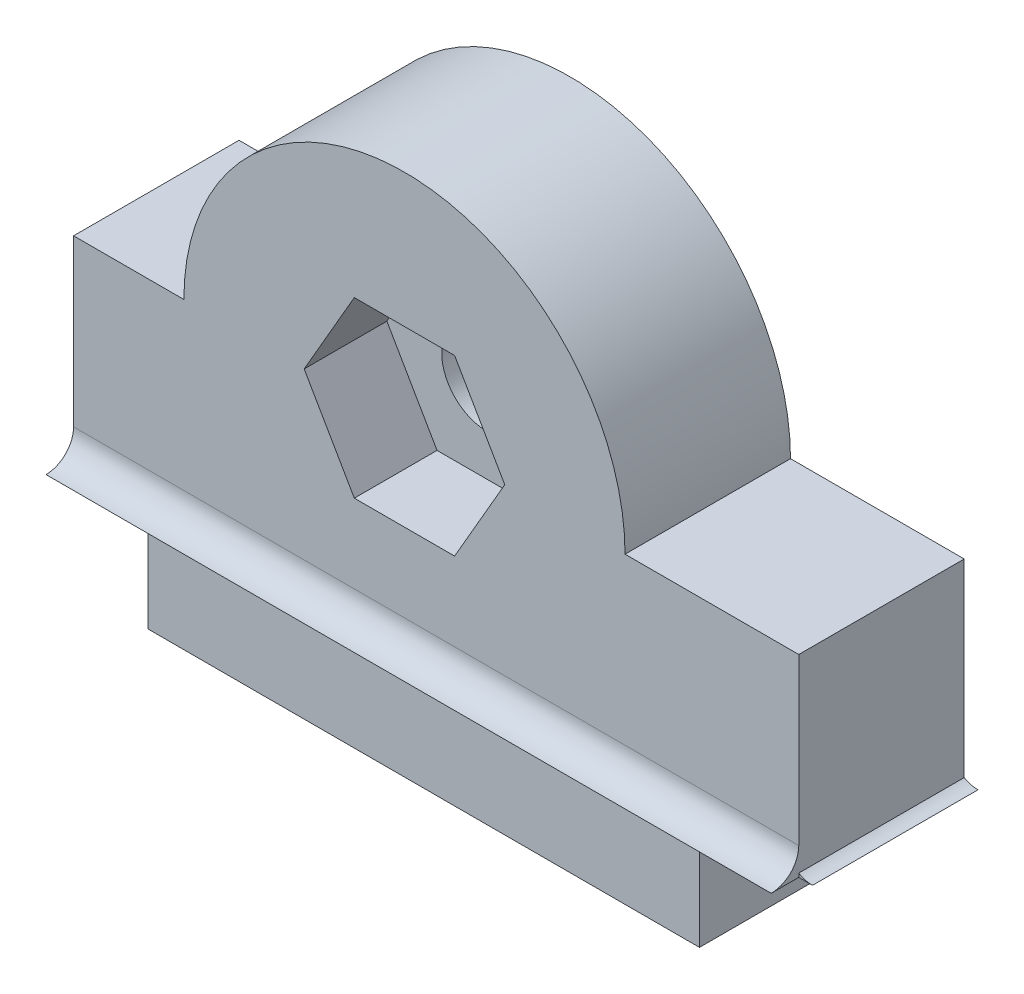
SolidWorks part; units mm, degrees
ref_plane "Front Plane" through (0, 0, 0) normal (0, 0, 1) x (1, 0, 0)
ref_plane "Top Plane" through (0, 0, 0) normal (0, 1, 0) x (1, 0, 0)
ref_plane "Right Plane" through (0, 0, 0) normal (1, 0, 0) x (0, 0, -1)
sketch "Sketch1" plane through (0, 0, 0) normal (0, 0, 1) x (1, 0, 0)
  line L0 (0, 0) -> (20, 0)
  line L1 (0, 0) -> (0, 4)
  line L2 (20, 0) -> (20, 4)
  line L3 (0, 4) -> (-2.7, 4)
  line L4 (23.6, 11) -> (23.6, 4)
  line L5 (-2.7, 4) -> (-2.7, 11)
  line L6 (-2.7, 11) -> (1.3, 11)
  line L7 (17.3, 11) -> (23.6, 11)
  line L8 (23.6, 4) -> (20, 4)
  line L11 (11.1187, 14.15) -> (7.4813, 14.15)
  line L12 (7.4813, 14.15) -> (5.6627, 11)
  line L13 (5.6627, 11) -> (7.4813, 7.85)
  line L14 (7.4813, 7.85) -> (11.1187, 7.85)
  line L15 (11.1187, 7.85) -> (12.9373, 11)
  line L16 (12.9373, 11) -> (11.1187, 14.15)
  arc A0 (17.3, 11) -> (1.3, 11) centre (9.3, 11) ccw
  circle A1 centre (9.3, 11) radius 3.15 construction
  point P19 (10, 0)
  dimension "D4" = 6.3
  dimension "D6" = 20
  dimension "D9" = 4
  dimension "D5" = 23.6
  dimension "D7" = 2.7
  dimension "D2" = 7
extrude "Boss-Extrude1" add sketch "Sketch1" along normal blind 6
sketch "Sketch2" plane through (-2.7, 0, 0) normal (-1, 0, 0) x (0, 0, 1)
  line L0 (3, 0) -> (3, 7) construction
  line L1 (6, 4) -> (6, 5)
  line L2 (6, 4) -> (7, 4)
  line L3 (0, 4) -> (-1, 4) construction
  line L4 (0, 4) -> (0, 5) construction
  arc A0 (6, 5) -> (7, 4) centre (7, 5) ccw
  arc A1 (0, 5) -> (-1, 4) centre (-1, 5) cw construction
  dimension "D1" = 1
  dimension "D2" = 1
  dimension "D3" = 6
  dimension "D4" = 3
  dimension "D5" = 4
extrude "Boss-Extrude2" add sketch "Sketch2" against normal up to surface (26.3 mm away) up to face at (23.6, 7.5, 3)
sketch "Sketch4" plane through (0, 0, 6) normal (0, 0, 1) x (1, 0, 0)
  line L0 (10.8, 0) -> (10.8, 7) construction
  line L1 (23.1, 4) -> (23.1, 5)
  line L2 (23.1, 4) -> (24.1, 4)
  line L3 (-1.5, 4) -> (-2.5, 4)
  line L4 (-1.5, 4) -> (-1.5, 5)
  arc A0 (23.1, 5) -> (24.1, 4) centre (24.1, 5) ccw
  arc A1 (-1.5, 5) -> (-2.5, 4) centre (-2.5, 5) cw
  dimension "D1" = 1
  dimension "D2" = 1
  dimension "D3" = 10.8
  dimension "D4" = 12.3
  dimension "D5" = 4
extrude "Boss-Extrude3" add sketch "Sketch4" against normal up to surface (6 mm away) up to face at (10.04, 6.8, 0)
sketch "Sketch8" plane through (0, 0, 0) normal (0, 0, 1) x (1, 0, 0)
  line L0 (5.6627, 11) -> (12.9373, 11) construction
  line L1 (11.1187, 14.15) -> (7.4813, 14.15) construction
  line L4 (7.4813, 14.15) -> (5.6627, 11)
  line L5 (5.6627, 11) -> (7.4813, 7.85)
  line L6 (7.4813, 7.85) -> (11.1187, 7.85)
  line L7 (11.1187, 7.85) -> (12.9373, 11)
  line L8 (12.9373, 11) -> (11.1187, 14.15)
  line L9 (11.1187, 14.15) -> (7.4813, 14.15)
  circle A0 centre (9.3, 11) radius 3.15 construction
  circle A1 centre (9.3, 11) radius 1.65
  point P4 (9.3, 11)
  point P6 (9.3, 7.85)
  point P14 (9.3, 14.15)
  dimension "D1" = 6.3
  dimension "D2" = 3.3
extrude "Boss-Extrude4" add sketch "Sketch8" along normal blind 3
equation "\"D4@Sketch1\" = 6 + \"tol1@parametersSketch@prostheticParameters.SLDPRT\""
equation "\"D1@Sketch8\"= 6 + \"tol1@parametersSketch@prostheticParameters.SLDPRT\""
equation "\"D2@Sketch8\"= 3 + \"tol1@parametersSketch@prostheticParameters.SLDPRT\""
